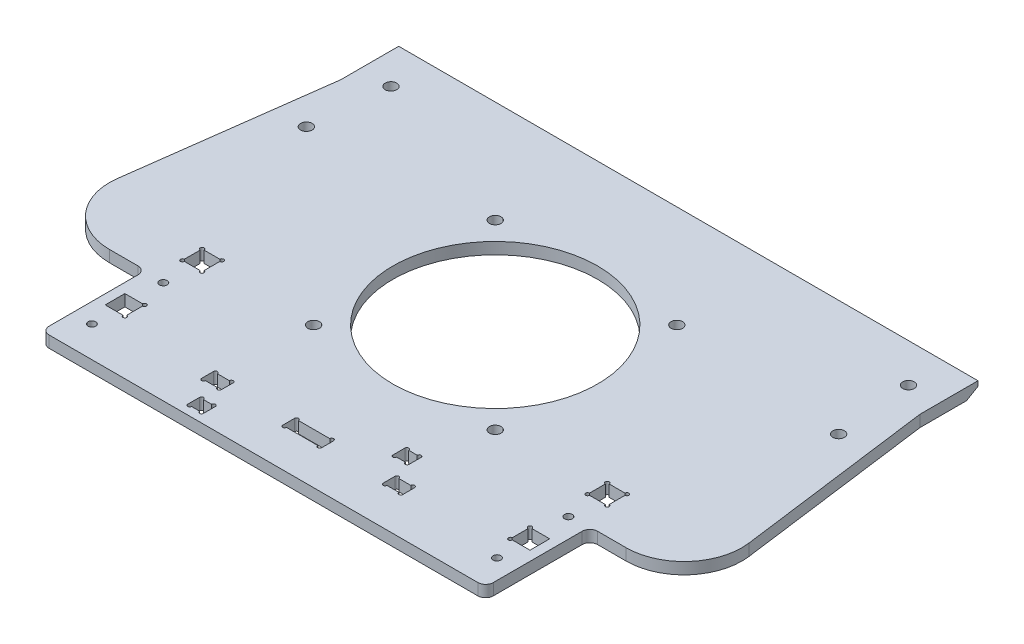
SolidWorks part; units mm, degrees
ref_plane "Front Plane" through (0, 0, 0) normal (0, 0, 1) x (1, 0, 0)
ref_plane "Top Plane" through (0, 0, 0) normal (0, 1, 0) x (1, 0, 0)
ref_plane "Right Plane" through (0, 0, 0) normal (1, 0, 0) x (0, 0, -1)
sketch "Sketch1" plane through (0, 0, 0) normal (0, 1, 0) x (1, 0, 0)
  line L0 (75, 95) -> (75, 110)
  line L1 (57.5, 27) -> (57.5, 19.1)
  line L2 (57.5, 27) -> (84, 27)
  line L3 (75, 95) -> (84, 27)
  line L4 (75, 110) -> (-75, 110)
  line L5 (0, 110) -> (0, 0) construction
  line L6 (57.5, 0) -> (-57.5, 0)
  line L7 (-57.5, 14) -> (-55, 14) construction
  line L8 (-57.5, 27) -> (-84, 27)
  line L9 (-75, 95) -> (-75, 110)
  line L10 (-75, 95) -> (-84, 27)
  line L11 (55, 19.1) -> (49.9, 19.1)
  line L12 (49.9, 19.1) -> (49.9, 14)
  line L13 (49.9, 14) -> (55, 14)
  line L14 (57.5, 14) -> (57.5, 0)
  line L15 (-57.5, 19.1) -> (-55, 19.1) construction
  line L16 (55, 34) -> (49.9, 34)
  line L17 (55, 34) -> (55, 39.1)
  line L18 (55, 39.1) -> (49.9, 39.1)
  line L19 (49.9, 34) -> (49.9, 39.1)
  line L20 (-55, 19.1) -> (-55, 14)
  line L21 (-57.5, 19.1) -> (-57.5, 14)
  line L22 (-49.9, 34) -> (-49.9, 39.1)
  line L23 (-55, 39.1) -> (-49.9, 39.1)
  line L24 (-55, 34) -> (-55, 39.1)
  line L25 (-55, 34) -> (-49.9, 34)
  line L26 (-57.5, 14) -> (-57.5, 0)
  line L27 (57.5, 19.1) -> (57.5, 14)
  line L28 (55, 19.1) -> (55, 14)
  line L29 (57.5, 19.1) -> (55, 19.1) construction
  line L30 (57.5, 14) -> (55, 14) construction
  line L31 (-49.9, 14) -> (-55, 14)
  line L32 (-49.9, 19.1) -> (-49.9, 14)
  line L33 (-55, 19.1) -> (-49.9, 19.1)
  line L34 (-57.5, 27) -> (-57.5, 19.1)
  dimension "D1" = 5.1
  dimension "D2" = 75
  dimension "D3" = 15
  dimension "D4" = 57.5
  dimension "D5" = 26.5
  dimension "D6" = 110
  dimension "D7" = 27
  dimension "D8" = 5.1
  dimension "D9" = 7
  dimension "D10" = 14
  dimension "D11" = 172.461
  dimension "D12" = 2.5
extrude "Boss-Extrude1" add sketch "Sketch1" along normal blind 3
sketch "Sketch2" plane through (0, 3, 0) normal (0, 1, 0) x (1, 0, 0)
  line L0 (0, 110) -> (0, 0) construction
  line L1 (75, 110) -> (-75, 110) construction
  line L2 (23.5113, 83.5113) -> (-23.5113, 36.4887) construction
  line L3 (-23.5113, 83.5113) -> (23.5113, 36.4887) construction
  line L4 (-4.9811, 60) -> (4.9811, 60) construction
  circle A0 centre (0, 60) radius 26.5
  circle A1 centre (23.5113, 83.5113) radius 1.5
  circle A2 centre (-23.5113, 83.5113) radius 1.5
  circle A3 centre (-23.5113, 36.4887) radius 1.5
  circle A4 centre (23.5113, 36.4887) radius 1.5
  dimension "D1" = 53
  dimension "D5" = 3
  dimension "D2" = 90
  dimension "D3" = 45
  dimension "D4" = 66.5
  dimension "D6" = 50
extrude "Cut-Extrude1" cut sketch "Sketch2" against normal blind 3
fillet "Fillet1" radius 15 2 edges at (84, 1.5, -27) (-84, 1.5, -27)
sketch "Sketch7" plane through (0, 0, 0) normal (0, -1, 0) x (1, 0, 0)
  line L0 (-22.05, -2.4) -> (-17.95, -2.4)
  line L1 (-22.05, -2.4) -> (-22.05, -5.5)
  line L2 (-22.05, -5.5) -> (-17.95, -5.5)
  line L3 (-17.95, -2.4) -> (-17.95, -5.5)
  line L4 (15.9, -17.6) -> (20.1, -17.6)
  line L5 (15.9, -17.6) -> (15.9, -20.7)
  line L6 (15.9, -20.7) -> (20.1, -20.7)
  line L7 (20.1, -17.6) -> (20.1, -20.7)
  line L8 (-26.05, -10) -> (-20.95, -10)
  line L9 (-26.05, -10) -> (-26.05, -13.1)
  line L10 (-26.05, -13.1) -> (-20.95, -13.1)
  line L11 (-20.95, -10) -> (-20.95, -13.1)
  line L12 (20.95, -10) -> (26.05, -10)
  line L13 (20.95, -10) -> (20.95, -13.1)
  line L14 (20.95, -13.1) -> (26.05, -13.1)
  line L15 (26.05, -10) -> (26.05, -13.1)
  line L16 (-5.05, -10) -> (5.05, -10)
  line L17 (-5.05, -10) -> (-5.05, -13.1)
  line L18 (-5.05, -13.1) -> (5.05, -13.1)
  line L19 (5.05, -10) -> (5.05, -13.1)
  line L20 (-55, 0) -> (55, 0) construction
  line L21 (-55, 0) -> (-55, -39) construction
  line L22 (-55, -39) -> (55, -39) construction
  line L23 (55, 0) -> (55, -39) construction
  line L24 (0, 0) -> (0, -39) construction
  line L25 (-20, -2.4) -> (-20, -5.5) construction
  line L26 (-23.5, -10) -> (-23.5, -13.1) construction
  line L27 (0, -10) -> (0, -13.1) construction
  line L28 (23.5, -10) -> (23.5, -13.1) construction
  line L29 (18, -17.6) -> (18, -20.7) construction
  dimension "D1" = 20
  dimension "D2" = 23.5
  dimension "D3" = 23.5
  dimension "D4" = 18
  dimension "D5" = 2.4
  dimension "D6" = 10
  dimension "D7" = 10
  dimension "D8" = 10
  dimension "D9" = 17.6
  dimension "D10" = 10.1
  dimension "D11" = 5.1
  dimension "D12" = 110
  dimension "D13" = 39
  dimension "D14" = 4.2
  dimension "D15" = 5.1
  dimension "D16" = 4.1
  dimension "D17" = 3.1
extrude "Cut-Extrude4" cut sketch "Sketch7" against normal blind 10
sketch "Sketch4" plane through (0, 3, 0) normal (0, 1, 0) x (1, 0, 0)
  line L0 (55, 39.1) -> (49.9, 39.1) construction
  line L1 (55, 34) -> (55, 39.1) construction
  line L2 (49.9, 39.1) -> (49.9, 34) construction
  line L3 (49.9, 34) -> (55, 34) construction
  line L4 (49.9, 19.1) -> (55, 19.1) construction
  line L5 (49.9, 14) -> (49.9, 19.1) construction
  line L6 (0, 0) -> (0, 22.5564) construction
  line L7 (55, 14) -> (49.9, 14) construction
  line L8 (-5.05, 13.1) -> (5.05, 13.1) construction
  line L9 (5.05, 10) -> (-5.05, 10) construction
  line L14 (15.9, 20.7) -> (20.1, 20.7) construction
  line L15 (20.1, 17.6) -> (15.9, 17.6) construction
  line L16 (20.95, 13.1) -> (26.05, 13.1) construction
  line L17 (26.05, 10) -> (20.95, 10) construction
  line L18 (50.4, 39.1) -> (49.9, 39.1)
  line L19 (49.9, 39.1) -> (49.9, 38.6)
  line L20 (54.5, 39.1) -> (55, 39.1)
  line L21 (55, 39.1) -> (55, 38.6)
  line L22 (55, 34.5) -> (55, 34)
  line L23 (55, 34) -> (54.5, 34)
  line L24 (49.9, 34.5) -> (49.9, 34)
  line L25 (49.9, 34) -> (50.4, 34)
  line L26 (50.4, 34) -> (50.4373, 34.0074)
  line L27 (50.4, 19.1) -> (49.9, 19.1)
  line L28 (49.9, 19.1) -> (49.9, 18.6)
  line L29 (49.9, 18.6) -> (49.9737, 13.5816)
  line L30 (49.9, 14.5) -> (49.9, 14)
  line L31 (49.9, 14) -> (50.4, 14)
  line L32 (25.05, 13.1) -> (26.05, 13.1)
  line L33 (20.95, 13.1) -> (21.95, 13.1)
  line L34 (20.95, 10) -> (21.95, 10)
  line L35 (25.05, 10) -> (26.05, 10)
  line L36 (15.9, 20.7) -> (16.9, 20.7)
  line L37 (19.1, 20.7) -> (20.1, 20.7)
  line L38 (20.1, 17.6) -> (19.1, 17.6)
  line L39 (15.9, 17.6) -> (16.9, 17.6)
  line L40 (4.05, 13.1) -> (5.05, 13.1)
  line L41 (5.05, 10) -> (4.05, 10)
  line L42 (-5.05, 10) -> (-4.05, 10)
  line L43 (-4.05, 13.1) -> (-5.05, 13.1)
  line L44 (-22.05, 5.5) -> (-21.05, 5.5)
  line L45 (-18.95, 5.5) -> (-17.95, 5.5)
  line L46 (-17.95, 2.4) -> (-18.95, 2.4)
  line L47 (-22.05, 2.4) -> (-21.05, 2.4)
  line L48 (-25.05, 10) -> (-26.05, 10)
  line L49 (-20.95, 10) -> (-21.95, 10)
  line L50 (-20.95, 13.1) -> (-21.95, 13.1)
  line L51 (-25.05, 13.1) -> (-26.05, 13.1)
  line L52 (-49.9, 14) -> (-50.4, 14)
  line L53 (-49.9, 14.5) -> (-49.9, 14)
  line L54 (-49.9, 18.6) -> (-49.9737, 13.5816)
  line L55 (-49.9, 19.1) -> (-49.9, 18.6)
  line L56 (-50.4, 19.1) -> (-49.9, 19.1)
  line L57 (-50.4, 34) -> (-50.4373, 34.0074)
  line L58 (-49.9, 34) -> (-50.4, 34)
  line L59 (-49.9, 34.5) -> (-49.9, 34)
  line L60 (-55, 34) -> (-54.5, 34)
  line L61 (-55, 34.5) -> (-55, 34)
  line L62 (-55, 39.1) -> (-55, 38.6)
  line L63 (-54.5, 39.1) -> (-55, 39.1)
  line L64 (-49.9, 39.1) -> (-49.9, 38.6)
  line L65 (-50.4, 39.1) -> (-49.9, 39.1)
  arc A0 (54.5, 39.1) -> (55, 38.6) centre (55, 39.1) cw
  arc A1 (50.4, 39.1) -> (49.9, 38.6) centre (49.9, 39.1) ccw
  arc A2 (49.9, 34.5) -> (50.4, 34) centre (49.9, 34) ccw
  arc A3 (55, 34.5) -> (54.5, 34) centre (55, 34) cw
  arc A4 (50.4, 19.1) -> (49.9, 18.6) centre (49.9, 19.1) ccw
  arc A5 (49.9, 14.5) -> (50.4, 14) centre (49.9, 14) ccw
  arc A6 (-20.95, 10) -> (-21.95, 10) centre (-21.45, 10) cw
  arc A7 (-26.05, 10) -> (-25.05, 10) centre (-25.55, 10) ccw
  arc A8 (-26.05, 13.1) -> (-25.05, 13.1) centre (-25.55, 13.1) cw
  arc A9 (-20.95, 13.1) -> (-21.95, 13.1) centre (-21.45, 13.1) ccw
  arc A10 (-17.95, 5.5) -> (-18.95, 5.5) centre (-18.45, 5.5) ccw
  arc A11 (-22.05, 5.5) -> (-21.05, 5.5) centre (-21.55, 5.5) cw
  arc A12 (5.05, 13.1) -> (4.05, 13.1) centre (4.55, 13.1) ccw
  arc A13 (5.05, 10) -> (4.05, 10) centre (4.55, 10) cw
  arc A14 (-22.05, 2.4) -> (-21.05, 2.4) centre (-21.55, 2.4) ccw
  arc A15 (-17.95, 2.4) -> (-18.95, 2.4) centre (-18.45, 2.4) cw
  arc A16 (-5.05, 10) -> (-4.05, 10) centre (-4.55, 10) ccw
  arc A17 (-5.05, 13.1) -> (-4.05, 13.1) centre (-4.55, 13.1) cw
  arc A18 (-49.9, 14.5) -> (-50.4, 14) centre (-49.9, 14) cw
  arc A19 (-50.4, 19.1) -> (-49.9, 18.6) centre (-49.9, 19.1) cw
  arc A20 (-55, 34.5) -> (-54.5, 34) centre (-55, 34) ccw
  arc A21 (-49.9, 34.5) -> (-50.4, 34) centre (-49.9, 34) cw
  arc A22 (-50.4, 39.1) -> (-49.9, 38.6) centre (-49.9, 39.1) cw
  arc A23 (-54.5, 39.1) -> (-55, 38.6) centre (-55, 39.1) ccw
  arc A24 (20.1, 20.7) -> (19.1, 20.7) centre (19.6, 20.7) ccw
  arc A25 (15.9, 20.7) -> (16.9, 20.7) centre (16.4, 20.7) cw
  arc A26 (15.9, 17.6) -> (16.9, 17.6) centre (16.4, 17.6) ccw
  arc A27 (20.1, 17.6) -> (19.1, 17.6) centre (19.6, 17.6) cw
  arc A28 (20.95, 13.1) -> (21.95, 13.1) centre (21.45, 13.1) cw
  arc A29 (26.05, 13.1) -> (25.05, 13.1) centre (25.55, 13.1) ccw
  arc A30 (26.05, 10) -> (25.05, 10) centre (25.55, 10) cw
  arc A31 (20.95, 10) -> (21.95, 10) centre (21.45, 10) ccw
  dimension "D1" = 0.5
chamfer "Chamfer1" distance 3 angle 30 1 edges at (0, 0, -110) first distance on face at (0, 0, -11.55)
extrude "Cut-Extrude5" cut sketch "Sketch4" against normal blind 10 contours L18 A1 L19 | A0 L20 L21 | A3 L22 L23 | L24 A2 L25 | L28 L27 A4 | A5 L31 L30 | A25 L36 | A24 L37 | A27 L38 | A26 L39 | A28 L33 | A29 L32 | A30 L35 | A31 L34 | A12 L40 | A13 L41 | A17 L43 | A16 L42 | A10 L45 | A15 L46 | A14 L47 | A11 L44 | A6 L49 | A9 L50 | A8 L51 | A7 L48 | L55 L56 A19 | A18 L52 L53 | A22 L64 L65 | L58 L59 A21 | A23 L62 L63 | A20 L60 L61 region at (49.8293, 3, -39.1707) region at (55.0707, 3, -39.1707) region at (55.0707, 3, -33.9293) region at (49.8293, 3, -33.9293)
sketch "Sketch9" plane through (0, 3, 0) normal (0, 1, 0) x (1, 0, 0)
  line L0 (52.45, 34) -> (52.45, 0) construction
  line L1 (50.4, 34) -> (54.5, 34) construction
  line L2 (-57.5, 0) -> (57.5, 0) construction
  line L3 (55, 14) -> (50.4, 14) construction
  line L4 (0, 110) -> (0, 0) construction
  line L5 (75, 110) -> (-75, 110) construction
  line L6 (75, 95) -> (75, 110) construction
  line L7 (81.7542, 43.9681) -> (75, 95) construction
  circle A0 centre (52.45, 26.5) radius 1
  circle A1 centre (52.45, 8) radius 1
  circle A2 centre (67, 100) radius 1.5
  circle A3 centre (68.9155, 80) radius 1.5
  circle A4 centre (-52.45, 8) radius 1
  circle A5 centre (-52.45, 26.5) radius 1
  circle A6 centre (-68.9155, 80) radius 1.5
  circle A7 centre (-67, 100) radius 1.5
  dimension "D1" = 2
  dimension "D4" = 3
  dimension "D5" = 10
  dimension "D2" = 7.5
  dimension "D3" = 6
  dimension "D6" = 8
  dimension "D7" = 15
  dimension "D8" = 8
  dimension "D9" = 5
extrude "Cut-Extrude6" cut sketch "Sketch9" against normal blind 10
fillet "Fillet3" radius 2 4 edges at (-57.5, 1.5, -27) (-57.5, 1.5, 0) (57.5, 1.5, 0) (57.5, 1.5, -27)
